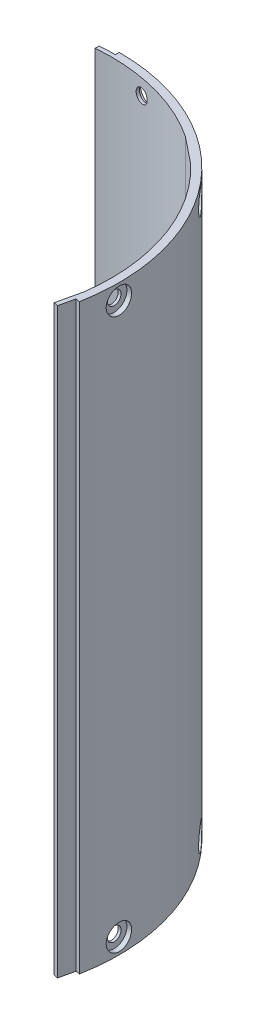
SolidWorks part; units mm, degrees
ref_plane "Спереди" through (0, 0, 0) normal (0, 0, 1) x (1, 0, 0)
ref_plane "Сверху" through (0, 0, 0) normal (0, 1, 0) x (1, 0, 0)
ref_plane "Справа" through (0, 0, 0) normal (1, 0, 0) x (0, 0, -1)
sketch "Эскиз2" plane through (0, 0, 0) normal (0, 1, 0) x (1, 0, 0)
  line L0 (0, -1000) -> (0, 49000) construction
  line L2 (33.9524, 35.3303) -> (27.0476, 40.8587) construction
  line L3 (48.5627, -6.5315) -> (46.5973, -15.1557) construction
  line L5 (33.9524, 35.3303) -> (27.0476, 40.8587)
  line L6 (48.5627, -6.5315) -> (46.5973, -15.1557) construction
  line L7 (-3.9968, 48.8367) -> (-3.9968, 49.84)
  line L10 (0, 50) -> (0, 49) construction
  line L12 (0, 0) -> (47.58, -10.8436) construction
  line L13 (50.1312, -9.3737) -> (49.0969, -9.138)
  line L14 (49.0969, -9.138) -> (48.2081, -13.038)
  line L15 (48.2081, -13.038) -> (47.1356, -12.7936)
  line L16 (47.58, -10.8436) -> (49.725, -11.3324) construction
  line L17 (47.1356, -12.7936) -> (48.5627, -6.5315)
  line L19 (0, 50) -> (0, 51)
  circle A0 centre (0, 0) radius 51 construction
  arc A1 (50.1312, -9.3737) -> (0, 51) centre (0, 0) ccw
  circle A2 centre (0, 0) radius 51 construction
  arc A3 (48.5627, -6.5315) -> (33.9524, 35.3303) centre (0, 0) ccw construction
  arc A4 (0, 51) -> (0, -51) centre (0, 0) ccw construction
  arc A5 (48.5627, -6.5315) -> (33.9524, 35.3303) centre (0, 0) ccw
  arc A6 (-3.9968, 48.8367) -> (27.0476, 40.8587) centre (0, 0) cw
  arc A7 (0, -51) -> (49.725, -11.3324) centre (0, 0) ccw construction
  arc A8 (49.725, -11.3324) -> (50.1312, -9.3737) centre (0, 0) ccw construction
  arc A9 (27.0476, 40.8587) -> (-27.0476, 40.8587) centre (0, 0) ccw construction
  arc A10 (0, 50) -> (-3.9968, 49.84) centre (0, 0) ccw
  point P25 (48.6525, -11.088)
  dimension "D1" = 3.9968
extrude "Бобышка-Вытянуть2" add sketch "Эскиз2" along normal up to surface (149 mm away)
ref_plane "Плоскость5" through (51, 0, 0) normal (1, 0, 0) x (0, 0, -1)
sketch "Эскиз15" plane through (51, 0, 0) normal (1, 0, 0) x (0, 0, -1)
  line L0 (0, -1000) -> (0, 49000) construction
  circle A0 centre (0, 4) radius 3.25
  dimension "D1" = 6.5
  dimension "D2" = 4
extrude "Вырез-Вытянуть5" cut sketch "Эскиз15" against normal blind 1.3
sketch "Эскиз16" plane through (49.7, 0, 0) normal (1, 0, 0) x (0, 0, -1)
  circle A0 centre (0, 4) radius 3.25 construction
  circle A1 centre (0, 4) radius 3.25 construction
  circle A2 centre (0, 4) radius 1.75
  dimension "D1" = 3.5
extrude "Вырез-Вытянуть6" cut sketch "Эскиз16" against normal through all
pattern_circular "Круговой массив3" count 5 every 20 about axis through (0, 0, 0) along (0, 1, 0) skipping 1, 3 of "Вырез-Вытянуть5", "Вырез-Вытянуть6"
sketch "Эскиз17" plane through (51, 0, 0) normal (1, 0, 0) x (0, 0, -1)
  line L0 (0, -1000) -> (0, 49000) construction
  line L1 (51, 149) -> (-9.3737, 149) construction
  circle A0 centre (0, 145) radius 3.25
  circle A1 centre (0, 4) radius 3.25 construction
  dimension "D1" = 4
extrude "Вырез-Вытянуть7" cut sketch "Эскиз17" against normal blind 1.3
sketch "Эскиз18" plane through (49.7, 0, 0) normal (1, 0, 0) x (0, 0, -1)
  circle A0 centre (0, 145) radius 3.25 construction
  circle A1 centre (0, 145) radius 3.25 construction
  circle A2 centre (0, 145) radius 1.75
  circle A3 centre (0, 4) radius 1.75 construction
extrude "Вырез-Вытянуть8" cut sketch "Эскиз18" against normal through all
pattern_circular "Круговой массив5" count 5 every 20 about axis through (0, 149, 0) along (0, 1, 0) skipping 1, 3 of "Вырез-Вытянуть8", "Вырез-Вытянуть7"
